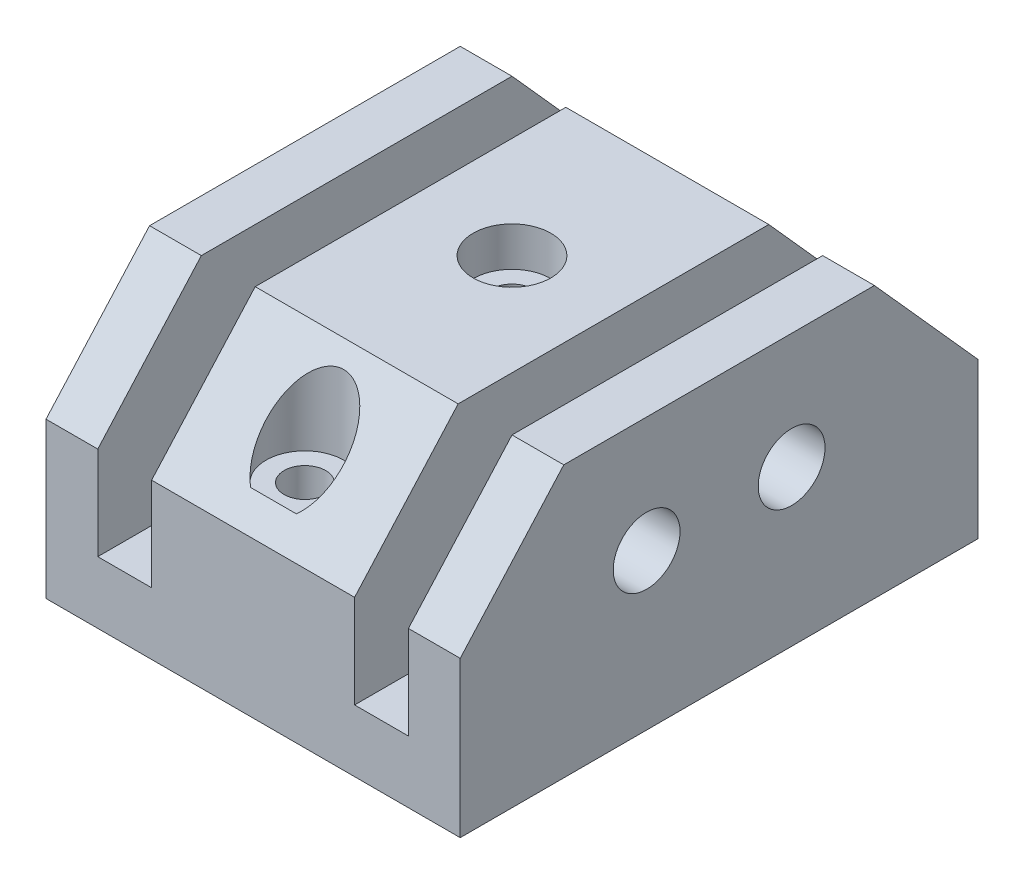
SolidWorks part; units mm, degrees
ref_plane "Front Plane" through (0, 0, 0) normal (0, 0, 1) x (1, 0, 0)
ref_plane "Top Plane" through (0, 0, 0) normal (0, 1, 0) x (1, 0, 0)
ref_plane "Right Plane" through (0, 0, 0) normal (1, 0, 0) x (0, 0, -1)
sketch "Sketch1" plane through (0, 0, 0) normal (1, 0, 0) x (0, 0, -1)
  line L1 (0, 0) -> (63.5, 0)
  line L2 (0, 0) -> (0, 6.35)
  line L3 (0, 6.35) -> (63.5, 6.35)
  line L4 (63.5, 0) -> (63.5, 6.35)
  dimension "D1" = 6.35
  dimension "D2" = 63.5
extrude "Boss-Extrude1" add sketch "Sketch1" against normal blind 50.8
sketch "Sketch2" plane through (0, 0, 0) normal (1, 0, 0) x (0, 0, -1)
  line L0 (0, 6.35) -> (0, 19.05)
  line L1 (0, 19.05) -> (12.7, 33.249)
  line L2 (12.7, 33.249) -> (50.8, 33.249)
  line L3 (50.8, 33.249) -> (63.5, 19.05)
  line L4 (63.5, 19.05) -> (63.5, 6.35)
  line L5 (63.5, 6.35) -> (0, 6.35)
  point P7 (31.75, 33.249)
  point P10 (31.75, 6.35)
  dimension "D1" = 38.1
  dimension "D2" = 12.7
  dimension "D3" = 12.7
  dimension "D4" = 19.05
  dimension "D5" = 19.05
extrude "Boss-Extrude2" add sketch "Sketch2" against normal blind 50.8
sketch "Sketch10" plane through (0, 0, -63.5) normal (0, 0, -1) x (-1, 0, 0)
  line L1 (50.8, 33.249) -> (0, 33.249) construction
  line L3 (6.35, 7.62) -> (6.35, 33.249)
  line L4 (6.35, 33.249) -> (12.954, 33.249)
  line L5 (12.954, 7.62) -> (12.954, 33.249)
  line L6 (6.35, 7.62) -> (12.954, 7.62)
  line L8 (50.8, 0) -> (0, 0) construction
  point P11 (12.954, 7.62)
  dimension "D1" = 7.62
  dimension "D2" = 6.604
  dimension "D3" = 6.35
extrude "Cut-Extrude1" cut sketch "Sketch10" against normal through all
pattern_linear "LPattern3" count 2 spacing 31.496 along (-1, 0, 0) of "Cut-Extrude1"
sketch "Sketch11" plane through (0, 0, 0) normal (1, 0, 0) x (0, 0, -1)
  circle A0 centre (22.86, 19.05) radius 4.0957
  circle A1 centre (22.86, 19.05) radius 7.9375 construction
  circle A2 centre (40.64, 19.05) radius 4.0958
  circle A3 centre (40.64, 19.05) radius 7.9375 construction
  dimension "D1" = 8.1915
  dimension "D3" = 15.875
  dimension "D4" = 8.1915
  dimension "D6" = 15.875
  dimension "D2" = 10.16
  dimension "D5" = 10.16
extrude "Cut-Extrude2" cut sketch "Sketch11" against normal through all
sketch "Sketch14" plane through (0, 33.249, 0) normal (0, 1, 0) x (1, 0, 0)
  line L3 (-37.846, 12.7) -> (-37.846, 50.8) construction
  point P0 (-25.4, 31.75)
  point P4 (-37.846, 31.75)
  dimension "D1" = 12.446
hole_wizard "CBORE for #10 Socket Head Cap Screw1" positions "Sketch15" profile "Sketch16" counterbore size "#10" standard "ANSI Inch" end condition up to next
sketch "Sketch15" plane through (0, 33.249, 0) normal (0, 1, 0) x (1, 0, 0)
  point P0 (-25.4, 31.75)
sketch "Sketch16" plane through (-25.4, 33.249, -31.75) normal (1, 0, 0) x (0, 0, 1)
  line L0 (0, 0) -> (0, 33.249)
  line L1 (0, 33.249) -> (2.5527, 33.249)
  line L3 (2.5527, 33.249) -> (2.5527, 4.826)
  line L4 (2.5527, 4.826) -> (4.7625, 4.826)
  line L5 (4.7625, 4.826) -> (4.7625, 0)
  line L7 (4.7625, 0) -> (0, 0)
  line L11 (0, -6.35) -> (0, 107.95) construction
  dimension "Thru Hole Dia." = 5.1054
  dimension "Thru Hole Depth" = 33.249
  dimension "C'Bore Dia." = 9.525
  dimension "C'Bore Depth" = 4.826
sketch "Sketch17" plane through (0, 40.0201, -44.7438) normal (0, 0.6667, -0.7454) x (-1, 0, 0)
  line L0 (12.954, -28.1343) -> (12.954, -9.0843) construction
  line L1 (37.846, -9.0843) -> (12.954, -9.0843) construction
  point P0 (25.4, -18.6093)
  point P1 (22.4146, -41.3668)
  point P4 (12.954, -18.6093)
  point P7 (25.4, -9.0843)
  point P8 (0, 0)
  point P9 (0, 0)
  point P10 (-64072.0164, 690029.433)
  point P11 (0, 0)
sketch "Sketch18" plane through (0, 8.4667, 9.466) normal (0, 0.6667, 0.7454) x (1, 0, 0)
  line L0 (-12.954, 33.249) -> (-12.954, 14.199) construction
  line L1 (-37.846, 33.249) -> (-12.954, 33.249) construction
  point P0 (-25.4, 23.724)
  point P1 (-25.4, 23.724)
  point P4 (-12.954, 23.724)
  point P7 (-25.4, 33.249)
ref_plane "Plane2" through (0, 33.02, 0) normal (0, -1, 0) x (-1, 0, 0)
hole_wizard "CBORE for #10 Socket Head Cap Screw3" positions "Sketch24" profile "Sketch25" counterbore size "#10" standard "ANSI Inch" end condition up to next
sketch "Sketch24" plane through (0, 33.02, 0) normal (0, -1, 0) x (-1, 0, 0)
  point P0 (25.4, 6.35)
  point P2 (25.4, 57.15)
sketch "Sketch25" plane through (-25.4, 33.02, -6.35) normal (1, 0, 0) x (0, 0, 1)
  line L0 (0, 0) -> (0, 33.02)
  line L1 (0, 33.02) -> (2.5527, 33.02)
  line L3 (2.5527, 33.02) -> (2.5527, 11.176)
  line L4 (2.5527, 11.176) -> (4.7625, 11.176)
  line L5 (4.7625, 11.176) -> (4.7625, 0)
  line L7 (4.7625, 0) -> (0, 0)
  line L11 (0, -6.35) -> (0, 107.95) construction
  dimension "Thru Hole Dia." = 5.1054
  dimension "Thru Hole Depth" = 33.02
  dimension "C'Bore Dia." = 9.525
  dimension "C'Bore Depth" = 11.176
